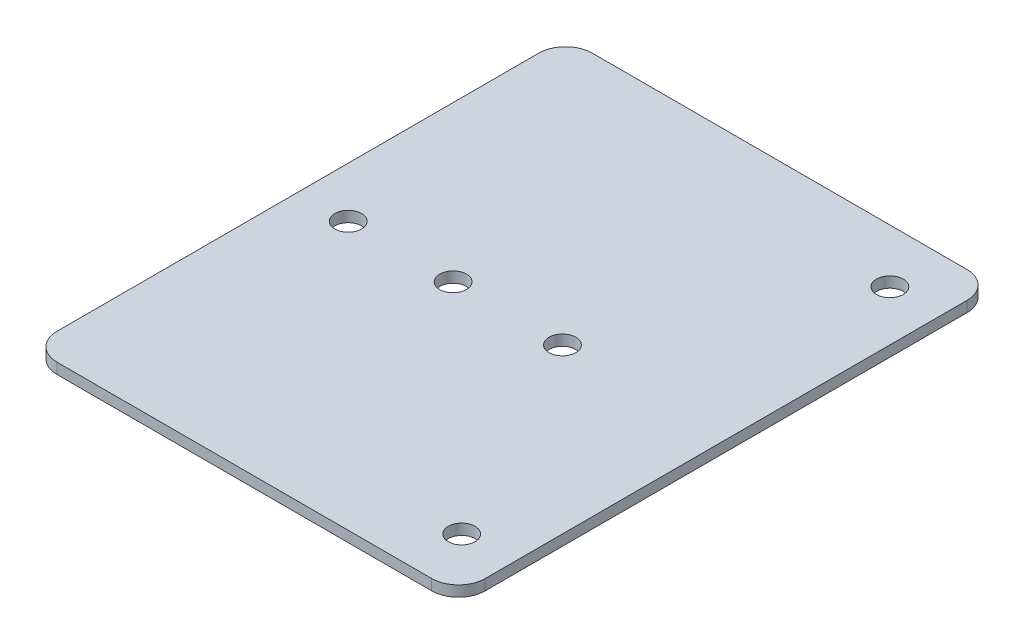
SolidWorks part; units mm, degrees
material "ABS"
ref_plane "Front Plane" through (0, 0, 0) normal (0, 0, 1) x (1, 0, 0)
ref_plane "Top Plane" through (0, 0, 0) normal (0, 1, 0) x (1, 0, 0)
ref_plane "Right Plane" through (0, 0, 0) normal (1, 0, 0) x (0, 0, -1)
sketch "Sketch1" plane through (0, 0, 0) normal (0, 1, 0) x (1, 0, 0)
  line L9 (30.6, 0) -> (-30.6, 0) construction
  line L10 (-35, 50) -> (35, 50)
  line L11 (-40, 45) -> (-40, -45)
  line L12 (-35, -50) -> (35, -50)
  line L13 (40, 45) -> (40, -45)
  line L14 (-40, 50) -> (40, -50) construction
  line L15 (-40, -50) -> (40, 50) construction
  line L17 (30.6, 40) -> (30.6, -40) construction
  line L20 (-18, 19.52) -> (12, 19.52) construction
  line L21 (-18, 27.92) -> (16.42, 27.92) construction
  line L22 (-18, 27.92) -> (-18, 19.52) construction
  line L23 (-18, -5.5) -> (16.42, -5.5) construction
  line L24 (16.42, 27.92) -> (16.42, -5.5) construction
  line L25 (-0.79, -5.5) -> (-0.79, 14.52) construction
  line L26 (12, 19.52) -> (12, 14.52) construction
  line L27 (12, 14.52) -> (-18, 14.52) construction
  line L28 (-18, 14.52) -> (-18, -5.5) construction
  line L29 (0, 27.92) -> (0, 0) construction
  arc A0 (35, 50) -> (40, 45) centre (35, 45) cw
  arc A1 (35, -50) -> (40, -45) centre (35, -45) ccw
  arc A2 (-40, -45) -> (-35, -50) centre (-35, -45) ccw
  arc A3 (-35, 50) -> (-40, 45) centre (-35, 45) ccw
  circle A4 centre (-30.6, 0) radius 2.5
  circle A5 centre (30.6, 40) radius 2.5
  circle A6 centre (30.6, -40) radius 2.5
  circle A7 centre (9.42, 0) radius 2.5
  circle A8 centre (-11, 0) radius 2.5
  point P0 (0, 0)
  point P19 (-88.2591, 22.0562)
  point P25 (0, 0)
  point P26 (-11, 0)
  point P31 (-18, -5.5)
  dimension "D7" = 34.42
  dimension "D3" = 5
  dimension "D5" = 5
  dimension "D14" = 5
  dimension "D1" = 80
  dimension "D2" = 100
  dimension "D4" = 80
  dimension "D6" = 61.2
  dimension "D8" = 33.42
  dimension "D9" = 30
  dimension "D10" = 8.4
  dimension "D11" = 5
  dimension "D12" = 5.5
  dimension "D13" = 7
  dimension "D15" = 18
extrude "Boss-Extrude1" add sketch "Sketch1" along normal blind 2
sketch "Sketch6" plane through (0, 2, 0) normal (0, 1, 0) x (1, 0, 0)
  line L0 (-36.4704, -29.7789) -> (28.5296, -49.7789)
  line L1 (-40, 45) -> (-40, -45) construction
  line L2 (-35, -50) -> (35, -50) construction
  line L3 (-40, 0) -> (40, 0) construction
  line L4 (40, -45) -> (40, 45) construction
  line L5 (-40, -25) -> (-40, -50)
  line L6 (-40, -50) -> (30, -50)
  line L7 (-40, 50) -> (30, 50)
  line L8 (-40, 25) -> (-40, 50)
  line L9 (-36.4704, 29.7789) -> (28.5296, 49.7789)
  arc A1 (-40, -25) -> (-36.4704, -29.7789) centre (-35, -25) ccw
  arc A2 (28.5296, -49.7789) -> (30, -50) centre (30, -45) ccw
  arc A3 (28.5296, 49.7789) -> (30, 50) centre (30, 45) cw
  arc A4 (-40, 25) -> (-36.4704, 29.7789) centre (-35, 25) cw
  dimension "D1" = 10
  dimension "D2" = 10
  dimension "D3" = 25
  dimension "D4" = 10
